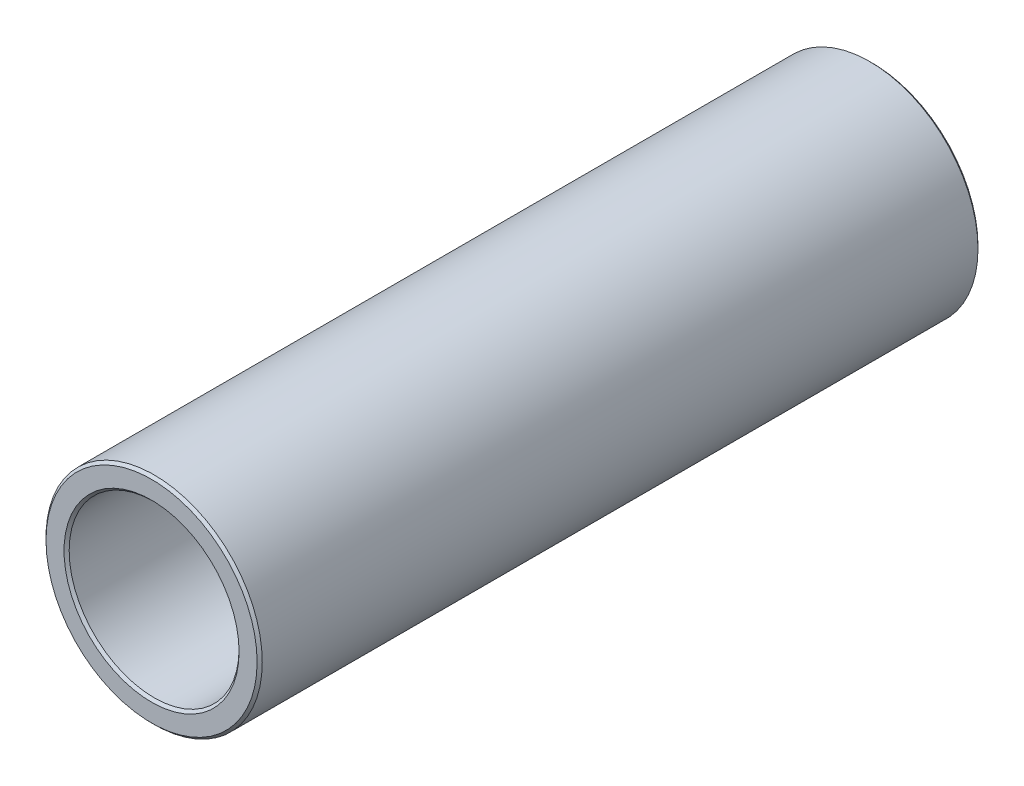
SolidWorks part; units mm, degrees
ref_plane "Płaszczyzna przednia" through (0, 0, 0) normal (0, 0, 1) x (1, 0, 0)
ref_plane "Płaszczyzna górna" through (0, 0, 0) normal (0, 1, 0) x (1, 0, 0)
ref_plane "Płaszczyzna prawa" through (0, 0, 0) normal (1, 0, 0) x (0, 0, -1)
sketch "Szkic1" plane through (0, 0, 0) normal (1, 0, 0) x (0, 0, -1)
  line L0 (-140, 0) -> (-140, 21)
  line L1 (-140, 21) -> (0, 21)
  line L2 (0, 21) -> (0, 0)
  line L3 (0, 0) -> (-140, 0)
  line L4 (0, 0) -> (-140, 0) construction
sketch "Szkic2" plane through (0, 0, 0) normal (1, 0, 0) x (0, 0, -1)
  line L0 (-140, 20.5) -> (-139.5, 21)
  line L1 (-139.5, 21) -> (-140, 21)
  line L2 (-140, 21) -> (-140, 20.5)
  line L3 (0, 0) -> (-140, 0) construction
sketch "Szkic3" plane through (0, 0, 0) normal (1, 0, 0) x (0, 0, -1)
  line L0 (-0.5, 21) -> (0, 20.5)
  line L1 (0, 20.5) -> (0, 21)
  line L2 (0, 21) -> (-0.5, 21)
  line L3 (0, 0) -> (-140, 0) construction
sketch "Szkic4" plane through (0, 0, 0) normal (1, 0, 0) x (0, 0, -1)
  line L0 (-13, 0) -> (-13, 16.5)
  line L1 (-13, 16.5) -> (-11.9175, 6.9175)
  line L2 (-11.9175, 6.9175) -> (-1.0825, 6.9175)
  line L3 (-1.0825, 6.9175) -> (0, 8)
  line L4 (0, 8) -> (0, 0)
  line L5 (0, 0) -> (-13, 0)
  line L6 (0, 0) -> (-13, 0) construction
sketch "Szkic5" plane through (0, 0, 0) normal (1, 0, 0) x (0, 0, -1)
  line L0 (-140, 0) -> (-140, 17)
  line L1 (-140, 17) -> (-139.5, 16.5)
  line L2 (-139.5, 16.5) -> (-13, 16.5)
  line L3 (-13, 16.5) -> (-13, 0)
  line L4 (-13, 0) -> (-140, 0)
  line L5 (-13, 0) -> (-140, 0) construction
revolve "Obrót1" add sketch "Szkic1" angle 360 about L4 reverse direction yes
revolve "Wycięcie-obrót1" cut sketch "Szkic2" angle 360 about L3 reverse direction yes
revolve "Wycięcie-obrót2" cut sketch "Szkic3" angle 360 about L3 reverse direction yes
revolve "Wycięcie-obrót3" cut sketch "Szkic4" angle 360 about L6 reverse direction yes
cosmetic thread "Oznaczenie gwintu1" parameters "D1"=12.0398, "D2"=16
cosmetic thread "Oznaczenie gwintu2" parameters "D2"=16
revolve "Wycięcie-obrót4" cut sketch "Szkic5" angle 360 about L5 reverse direction yes
ref_plane "Płaszczyzna1" through (0, 0, 140) normal (0, 0, 1) x (1, 0, 0)
ref_plane "IP2 XY" through (0, 0, 140) normal (0, 0, 1) x (1, 0, 0)
ref_plane "IP2 XZ" through (0, 0, 0) normal (0, -1, 0) x (-1, 0, 0)
ref_plane "IP2 YZ" through (0, 0, 0) normal (1, 0, 0) x (0, 0, -1)
ref_axis "IP2 X" through (-80.9, 0, 140) along (1, 0, 0)
ref_axis "IP2 Y" through (0, -50, 140) along (0, 1, 0)
ref_axis "IP2 Z" through (0, 0, 80.9) along (0, 0, -1)
sketch3d "IP2"
  point P0 (0, 0, 140)
ref_plane "IP1 XY" through (0, 0, 0) normal (0, 0, 1) x (1, 0, 0)
ref_plane "IP1 XZ" through (0, 0, 0) normal (0, -1, 0) x (-1, 0, 0)
ref_plane "IP1 YZ" through (0, 0, 0) normal (1, 0, 0) x (0, 0, -1)
ref_axis "IP1 X" through (-80.9, 0, 0) along (1, 0, 0)
ref_axis "IP1 Y" through (0, -50, 0) along (0, 1, 0)
ref_axis "IP1 Z" through (0, 0, 80.9) along (0, 0, -1)
sketch3d "IP1"
  point P0 (0, 0, 0)
